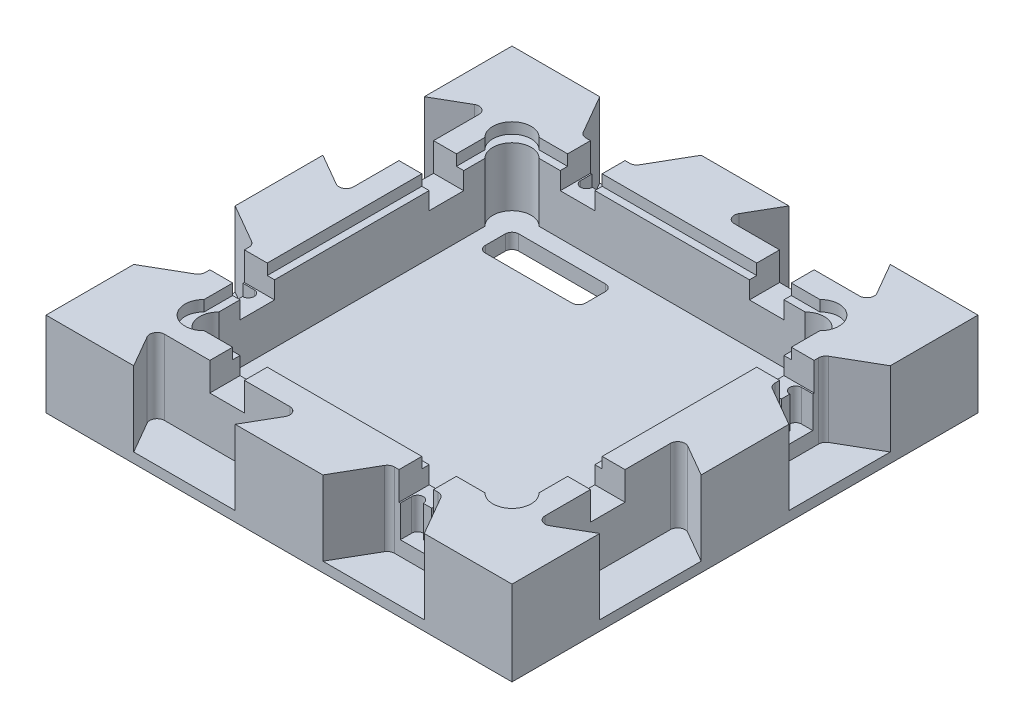
SolidWorks part; units mm, degrees
material "Macor"
ref_plane "Front Plane" through (0, 0, 0) normal (0, 0, 1) x (1, 0, 0)
ref_plane "Top Plane" through (0, 0, 0) normal (0, 1, 0) x (1, 0, 0)
ref_plane "Right Plane" through (0, 0, 0) normal (1, 0, 0) x (0, 0, -1)
sketch "Sketch1" plane through (0, 0, 0) normal (0, 1, 0) x (1, 0, 0)
  line L1 (-69.85, -69.85) -> (69.85, -69.85)
  line L2 (-69.85, -69.85) -> (-69.85, 69.85)
  line L3 (-69.85, 69.85) -> (69.85, 69.85)
  line L4 (69.85, -69.85) -> (69.85, 69.85)
  line L5 (-69.85, -69.85) -> (69.85, 69.85) construction
  line L6 (-69.85, 69.85) -> (69.85, -69.85) construction
  point P0 (0, 0)
  dimension "D1" = 139.7
extrude "Boss-Extrude1" add sketch "Sketch1" along normal mid plane 25.4
sketch "Sketch6" plane through (0, 12.7, 0) normal (0, 1, 0) x (1, 0, 0)
  line L0 (-48, 39.8683) -> (-48, -39.8683)
  line L1 (-48, -48) -> (48, -48) construction
  line L2 (-48, -48) -> (-48, 48) construction
  line L3 (-48, 48) -> (48, 48) construction
  line L4 (48, -48) -> (48, 48) construction
  line L5 (-48, -48) -> (48, 48) construction
  line L6 (-48, 48) -> (48, -48) construction
  line L7 (-39.8683, -48) -> (39.8683, -48)
  line L8 (39.8683, 48) -> (-39.8683, 48)
  line L9 (48, 39.8683) -> (48, -39.8683)
  arc A0 (-39.8683, 48) -> (-48, 39.8683) centre (-43.9341, 43.9341) ccw
  arc A1 (48, 39.8683) -> (39.8683, 48) centre (43.9341, 43.9341) ccw
  arc A2 (39.8683, -48) -> (48, -39.8683) centre (43.9341, -43.9341) ccw
  arc A3 (-48, -39.8683) -> (-39.8683, -48) centre (-43.9341, -43.9341) ccw
  point P0 (0, 0)
  point P21 (0, 0)
  dimension "D2" = 5.75
  dimension "D1" = 96
  dimension "D3" = 4
extrude "power_supply_component_depth" cut sketch "Sketch6" against normal offset from surface (20.9 mm away) 4.5 up to face at (0, -12.7, 0)
ref_axis "Axis1" through (0, -25.4398, 0) along (0, 1, 0)
sketch "Sketch4" plane through (0, 12.7, 0) normal (0, 1, 0) x (1, 0, 0)
  line L0 (-43.55, -69.85) -> (-50.9401, -57.05)
  line L1 (-69.85, -69.85) -> (69.85, -69.85) construction
  line L2 (-50.9401, -57.05) -> (-5.7599, -57.05)
  line L3 (-5.7599, -57.05) -> (-13.15, -69.85)
  line L4 (-13.15, -69.85) -> (-43.55, -69.85)
  line L5 (43.55, -69.85) -> (36.1599, -57.05)
  line L24 (43.55, -69.85) -> (13.15, -69.85)
  line L25 (-69.85, -69.85) -> (-43.55, -69.85) construction
  line L26 (-13.15, -69.85) -> (13.15, -69.85) construction
  line L27 (43.55, -69.85) -> (69.85, -69.85) construction
  line L28 (36.1599, -57.05) -> (20.5401, -57.05)
  line L30 (13.15, -69.85) -> (20.5401, -57.05)
  dimension "D1" = 60
  dimension "D2" = 30.4
  dimension "D3" = 12.8
  dimension "D4" = 60
  dimension "D5" = 26.3
extrude "Cut-Extrude6" cut sketch "Sketch4" against normal offset from surface (22.4 mm away) 3 up to face at (0, -12.7, 0)
sketch "Sketch8" plane through (0, 12.7, 0) normal (0, 1, 0) x (1, 0, 0)
  line L0 (-28.35, -57.05) -> (-28.35, -52.525) construction
  line L1 (-5.7599, -57.05) -> (-50.9401, -57.05) construction
  line L2 (28.35, -57.05) -> (28.35, -52.525) construction
  line L3 (36.1599, -57.05) -> (20.5401, -57.05) construction
  line L5 (-33.53, -57.05) -> (-23.17, -57.05)
  line L6 (-33.53, -57.05) -> (-33.53, -48)
  line L7 (-33.53, -48) -> (-23.17, -48)
  line L8 (-23.17, -57.05) -> (-23.17, -48)
  line L9 (-33.53, -57.05) -> (-23.17, -48) construction
  line L10 (-33.53, -48) -> (-23.17, -57.05) construction
  line L11 (36.1599, -57.05) -> (20.5401, -57.05) construction
  line L12 (23.17, -57.05) -> (33.53, -57.05)
  line L13 (23.17, -57.05) -> (23.17, -48)
  line L14 (23.17, -48) -> (33.53, -48)
  line L15 (33.53, -57.05) -> (33.53, -48)
  line L16 (23.17, -57.05) -> (33.53, -48) construction
  line L17 (23.17, -48) -> (33.53, -57.05) construction
  line L18 (-39.8683, -48) -> (39.8683, -48) construction
  dimension "D1" = 10.36
extrude "Cut-Extrude7" cut sketch "Sketch8" against normal blind 8.48
sketch "Sketch9" plane through (0, 4.22, 0) normal (0, 1, 0) x (1, 0, 0)
  line L0 (28.35, -57.05) -> (28.35, -55.3625) construction
  line L1 (36.1599, -57.05) -> (20.5401, -57.05) construction
  line L2 (27.085, -53.675) -> (29.615, -53.675)
  line L3 (23.585, -53.675) -> (33.115, -53.675) construction
  line L4 (23.585, -53.675) -> (23.585, -57.05)
  line L5 (23.585, -57.05) -> (33.115, -57.05)
  line L6 (33.115, -53.675) -> (33.115, -57.05)
  line L7 (23.585, -53.675) -> (33.115, -57.05) construction
  line L8 (23.585, -57.05) -> (33.115, -53.675) construction
  arc A0 (23.585, -53.675) -> (27.085, -53.675) centre (25.335, -53.675) cw
  arc A1 (33.115, -53.675) -> (29.615, -53.675) centre (31.365, -53.675) ccw
  dimension "D3" = 1.75
  dimension "D1" = 9.53
  dimension "D2" = 3.375
extrude "Cut-Extrude8" cut sketch "Sketch9" against normal blind 9.53
fillet "Fillet2" radius 2.2 4 edges at (20.5401, 1.5, 57.05) (36.1599, 1.5, 57.05) (-5.7599, 1.5, 57.05) (-50.9401, 1.5, 57.05)
pattern_circular "CirPattern5" count 4 over 360 about axis through (0, -25.4398, 0) along (0, 1, 0) of "Cut-Extrude6", "Cut-Extrude7", "Cut-Extrude8", "Fillet2"
sketch "Sketch10" plane through (0, 12.7, 0) normal (0, 1, 0) x (1, 0, 0)
  line L0 (-42.0683, 50.2) -> (42.0683, 50.2)
  line L1 (-50.2, -50.2) -> (50.2, -50.2) construction
  line L2 (-50.2, -50.2) -> (-50.2, 50.2) construction
  line L3 (-50.2, 50.2) -> (50.2, 50.2) construction
  line L4 (50.2, -50.2) -> (50.2, 50.2) construction
  line L5 (-50.2, -50.2) -> (50.2, 50.2) construction
  line L6 (-50.2, 50.2) -> (50.2, -50.2) construction
  line L7 (50.2, 42.0683) -> (50.2, -42.0683)
  line L8 (42.0683, -50.2) -> (-42.0683, -50.2)
  line L9 (-50.2, -42.0683) -> (-50.2, 42.0683)
  arc A0 (42.0683, 50.2) -> (50.2, 42.0683) centre (46.1341, 46.1341) cw
  arc A1 (50.2, -42.0683) -> (42.0683, -50.2) centre (46.1341, -46.1341) cw
  arc A2 (-42.0683, -50.2) -> (-50.2, -42.0683) centre (-46.1341, -46.1341) cw
  arc A3 (-50.2, 42.0683) -> (-42.0683, 50.2) centre (-46.1341, 46.1341) cw
  point P0 (0, 0)
  point P21 (0, 0)
  dimension "D2" = 5.75
  dimension "D1" = 100.4
  dimension "D3" = 4
extrude "Cut-Extrude9" cut sketch "Sketch10" against normal blind 3.25
sketch "Sketch12" plane through (0, -8.2, 0) normal (0, 1, 0) x (1, 0, 0)
  line L0 (39.8683, 48) -> (-39.8683, 48) construction
  line L1 (-43, 43) -> (-13, 43)
  line L2 (-43, 43) -> (-43, 33)
  line L3 (-43, 33) -> (-13, 33)
  line L4 (-13, 43) -> (-13, 33)
  line L5 (-48, 23.17) -> (-48, 33.53) construction
  dimension "D1" = 5
  dimension "D2" = 5
  dimension "D3" = 30
  dimension "D4" = 10
extrude "Cut-Extrude10" cut sketch "Sketch12" against normal through all and the other way through all
fillet "Fillet5" radius 2 4 edges at (-43, -10.45, -43) (-13, -10.45, -43) (-13, -10.45, -33) (-43, -10.45, -33)
pattern_circular "CirPattern6" count 2 over 360 about axis through (0, -25.4398, 0) along (0, 1, 0) of "Fillet5", "Cut-Extrude10"
sketch "sussy_baka_uwu" plane through (0, -8.2, 0) normal (0, 1, 0) x (1, 0, 0)
  line L0 (-13, 41) -> (-13, 35) construction
  line L1 (-15, 33) -> (-41, 33) construction
  line L2 (-43, 35) -> (-43, 41) construction
  line L3 (-41, 43) -> (-15, 43) construction
  line L4 (-13, 41) -> (-13, 35)
  line L5 (-15, 33) -> (-41, 33)
  line L6 (-43, 35) -> (-43, 41)
  line L7 (-41, 43) -> (-15, 43)
  line L8 (9.2262, 43) -> (9.2262, -5.178)
  line L9 (-35.7752, 33) -> (-35.7752, -5.178)
  line L10 (-35.7752, -5.178) -> (-25.7958, -5.178)
  line L11 (-25.7958, -5.178) -> (-25.7958, 3.1068)
  line L12 (-25.7958, 3.1068) -> (-3.3892, 3.1068)
  line L13 (-3.3892, 3.1068) -> (-3.3892, -5.178)
  line L14 (-3.3892, -5.178) -> (9.2262, -5.178)
  line L15 (9.2262, 39.0703) -> (19.3939, 39.0703)
  line L16 (19.3939, 39.0703) -> (19.3939, 12.333)
  line L17 (19.3939, 12.333) -> (9.2262, 12.333)
  arc A0 (-13, 41) -> (-15, 43) centre (-15, 41) ccw construction
  arc A1 (-15, 33) -> (-13, 35) centre (-15, 35) ccw construction
  arc A2 (-43, 35) -> (-41, 33) centre (-41, 35) ccw construction
  arc A3 (-41, 43) -> (-43, 41) centre (-41, 41) ccw construction
  arc A4 (-13, 41) -> (-15, 43) centre (-15, 41) ccw
  arc A5 (-15, 33) -> (-13, 35) centre (-15, 35) ccw
  arc A6 (-43, 35) -> (-41, 33) centre (-41, 35) ccw
  arc A7 (-41, 43) -> (-43, 41) centre (-41, 41) ccw
  arc A8 (-35.7752, 43) -> (9.2262, 43) centre (-13.2745, 42.7666) cw
equation "\"panel_width\"= 5.5in"
equation "\"finger_joint_width\"= 30mm"
equation "\"D1@Sketch1\"=\"panel_width\""
